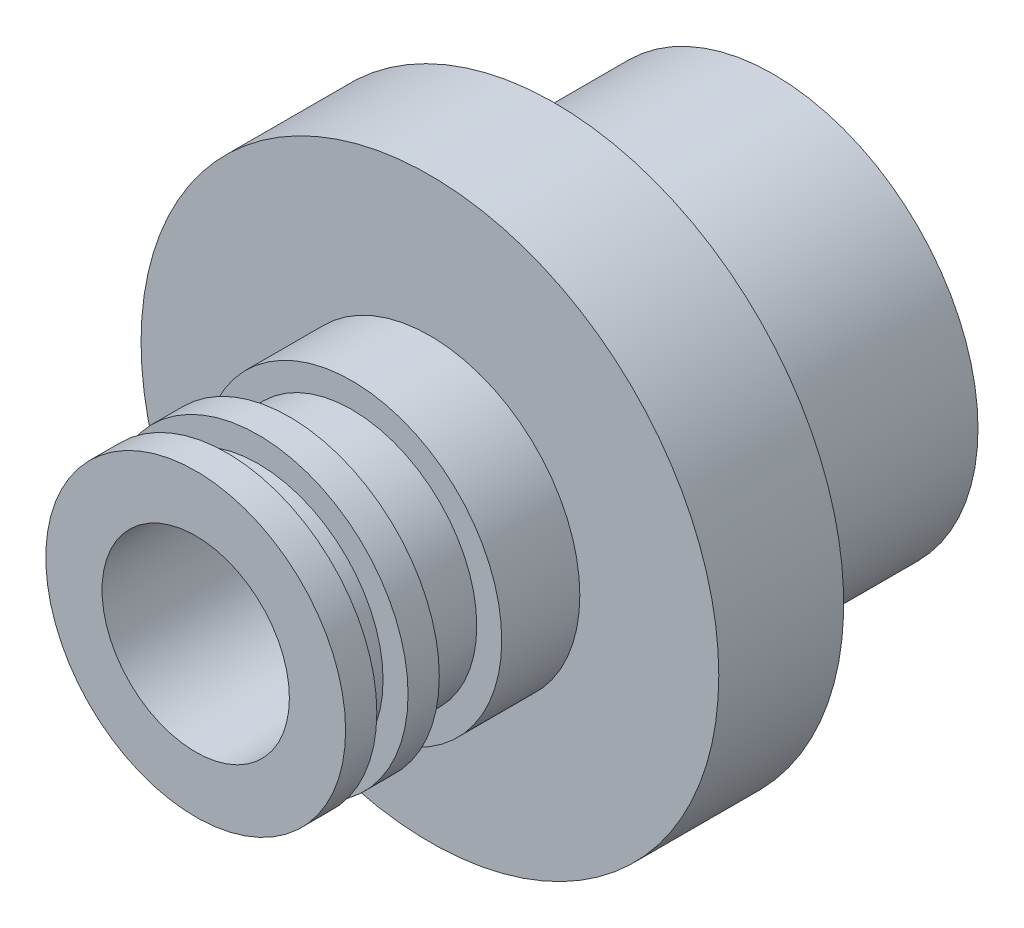
SolidWorks part; units mm, degrees
ref_plane "Front Plane" through (0, 0, 0) normal (0, 0, 1) x (1, 0, 0)
ref_plane "Top Plane" through (0, 0, 0) normal (0, 1, 0) x (1, 0, 0)
ref_plane "Right Plane" through (0, 0, 0) normal (1, 0, 0) x (0, 0, -1)
sketch "Sketch1" plane through (0, 0, 0) normal (0, 0, 1) x (1, 0, 0)
  circle A0 centre (0, 0) radius 3
  circle A1 centre (0, 0) radius 9.25
extrude "Boss-Extrude1" add sketch "Sketch1" along normal blind 18.5
sketch "Sketch2" plane through (0, 0, 18.5) normal (0, 0, 1) x (1, 0, 0)
  circle A0 centre (0, 0) radius 4.8
extrude "Cut-Extrude1" cut sketch "Sketch2" against normal blind 7.5 flip side to cut
sketch "Sketch3" plane through (0, 0, 18.5) normal (0, 0, 1) x (1, 0, 0)
  circle A0 centre (0, 0) radius 4
extrude "Cut-Extrude2" cut sketch "Sketch3" against normal blind 1 from offset 1 flip side to cut offset against normal yes
extrude "Cut-Extrude3" cut sketch "Sketch3<2>" against normal blind 2 from offset 3 flip side to cut offset against normal yes
sketch "Sketch3<2>" plane through (0, 0, 18.5) normal (0, 0, 1) x (1, 0, 0) same geometry as "Sketch3"
sketch "Sketch4" plane through (0, 0, 0) normal (0, 0, -1) x (-1, 0, 0)
  circle A0 centre (0, 0) radius 6.55
extrude "Cut-Extrude4" cut sketch "Sketch4" against normal blind 7 flip side to cut
